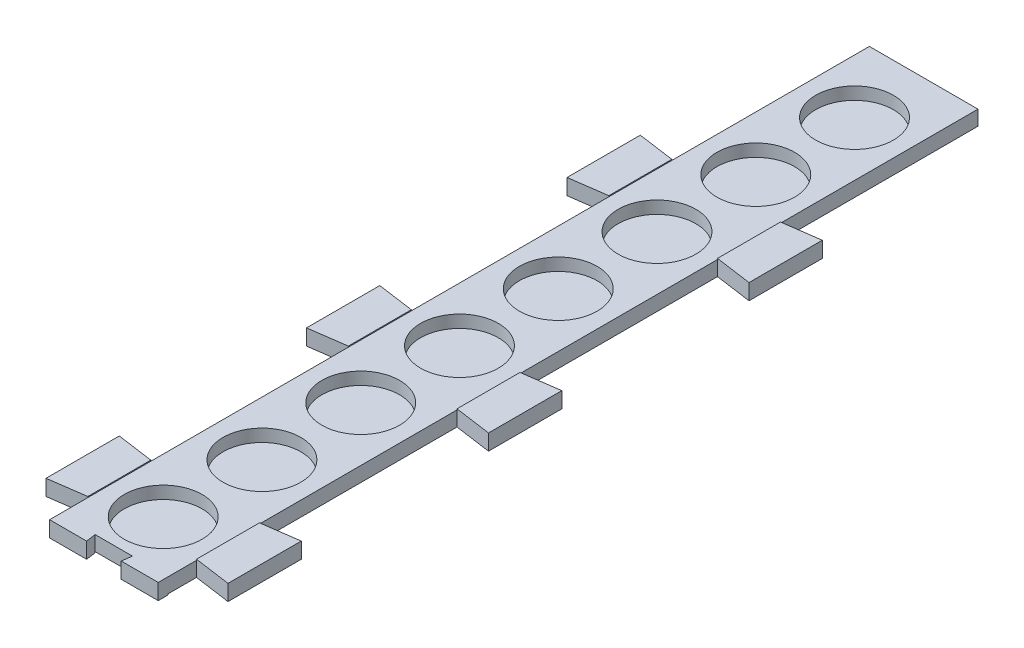
SolidWorks part; units mm, degrees
ref_plane "Front Plane" through (0, 0, 0) normal (0, 0, 1) x (1, 0, 0)
ref_plane "Top Plane" through (0, 0, 0) normal (0, 1, 0) x (1, 0, 0)
ref_plane "Right Plane" through (0, 0, 0) normal (1, 0, 0) x (0, 0, -1)
sketch "Sketch1" plane through (0, 0, 0) normal (0, 1, 0) x (1, 0, 0)
  line L1 (-13.97, -195.58) -> (13.97, -195.58)
  line L2 (-13.97, -195.58) -> (-13.97, 195.58)
  line L3 (-13.97, 195.58) -> (13.97, 195.58)
  line L4 (13.97, -195.58) -> (13.97, 195.58)
  line L5 (-13.97, -195.58) -> (13.97, 195.58) construction
  line L6 (-13.97, 195.58) -> (13.97, -195.58) construction
  point P0 (0, 0)
  dimension "D1" = 391.16
  dimension "D2" = 27.94
extrude "Boss-Extrude1" add sketch "Sketch1" along normal blind 3.81
sketch "Sketch2" plane through (0, 3.81, 0) normal (0, 1, 0) x (1, 0, 0)
  line L0 (-13.97, 195.58) -> (-13.97, -195.58) construction
  line L1 (13.97, 195.58) -> (-13.97, 195.58) construction
  line L3 (-13.97, -195.58) -> (13.97, -195.58) construction
  circle A0 centre (0, 177.8) radius 10
  circle A1 centre (0, 152.4) radius 10
  circle A2 centre (0, 127) radius 10
  circle A3 centre (0, 101.6) radius 10
  circle A4 centre (0, 76.2) radius 10
  circle A5 centre (0, 50.8) radius 10
  circle A6 centre (0, 25.4) radius 10
  circle A7 centre (0, 0) radius 10
  circle A8 centre (0, -25.4) radius 10
  circle A9 centre (0, -50.8) radius 10
  circle A10 centre (0, -76.2) radius 10
  circle A11 centre (0, -101.6) radius 10
  circle A12 centre (0, -127) radius 10
  circle A13 centre (0, -152.4) radius 10
  circle A14 centre (0, -177.8) radius 10
  dimension "D1" = 20
  dimension "D2" = 13.97
  dimension "D4" = 17.78
  dimension "D5" = 17.78
  dimension "D3" = 15
extrude "Cut-Extrude1" cut sketch "Sketch2" against normal blind 3.21
sketch "Sketch4" plane through (0, 0, 0) normal (0, 1, 0) x (1, 0, 0)
  line L0 (13.97, -56.2067) -> (23.4023, -54.881)
  line L2 (13.97, -195.58) -> (13.97, 195.58) construction
  line L5 (13.97, 144.78) -> (13.97, 128.5844)
  line L6 (0, 195.58) -> (0, -195.58) construction
  line L7 (13.97, 195.58) -> (-13.97, 195.58) construction
  line L8 (-13.97, -195.58) -> (13.97, -195.58) construction
  line L9 (13.97, -56.2067) -> (13.97, -72.4022)
  line L30 (-13.97, 144.78) -> (-13.97, 128.5844)
  line L31 (13.97, 144.78) -> (23.4023, 146.1056)
  line L32 (-13.97, 128.5844) -> (-23.4023, 127.2588)
  line L33 (13.97, 128.5844) -> (23.4023, 127.2588)
  line L34 (23.4023, 146.1056) -> (23.4023, 127.2588)
  line L35 (13.97, 144.78) -> (13.97, 128.5844)
  line L36 (13.97, 144.78) -> (13.97, 128.5844)
  line L37 (23.4023, 127.2588) -> (23.4023, 146.1056)
  line L38 (13.97, 144.78) -> (23.4023, 146.1056)
  line L39 (-13.97, 144.78) -> (-23.4023, 146.1056)
  line L40 (-23.4023, 127.2588) -> (-23.4023, 146.1056)
  line L41 (-23.4023, 146.1056) -> (-23.4023, 127.2588)
  line L42 (13.97, 77.7844) -> (23.4023, 79.1101)
  line L43 (13.97, 77.7844) -> (13.97, 61.5889)
  line L44 (13.97, 61.5889) -> (23.4023, 60.2633)
  line L45 (23.4023, 79.1101) -> (23.4023, 60.2633)
  line L46 (13.97, 10.7889) -> (23.4023, 12.1145)
  line L47 (13.97, 10.7889) -> (13.97, -5.4067)
  line L48 (13.97, -5.4067) -> (23.4023, -6.7323)
  line L49 (23.4023, 12.1145) -> (23.4023, -6.7323)
  line L50 (-13.97, 10.7889) -> (-13.97, -5.4067)
  line L51 (-13.97, -5.4067) -> (-23.4023, -6.7323)
  line L52 (-23.4023, 12.1145) -> (-23.4023, -6.7323)
  line L53 (-13.97, 10.7889) -> (-23.4023, 12.1145)
  line L54 (-13.97, 77.7844) -> (-13.97, 61.5889)
  line L55 (-13.97, 61.5889) -> (-23.4023, 60.2633)
  line L56 (-23.4023, 79.1101) -> (-23.4023, 60.2633)
  line L57 (-13.97, 77.7844) -> (-23.4023, 79.1101)
  line L58 (13.97, -72.4022) -> (23.4023, -73.7278)
  line L59 (23.4023, -54.881) -> (23.4023, -73.7278)
  line L60 (13.97, -123.2022) -> (23.4023, -121.8766)
  line L61 (13.97, -123.2022) -> (13.97, -139.3978)
  line L62 (13.97, -139.3978) -> (23.4023, -140.7234)
  line L63 (23.4023, -121.8766) -> (23.4023, -140.7234)
  line L72 (-13.97, -123.2022) -> (-13.97, -139.3978)
  line L73 (-13.97, -139.3978) -> (-23.4023, -140.7234)
  line L74 (-23.4023, -121.8766) -> (-23.4023, -140.7234)
  line L75 (-13.97, -123.2022) -> (-23.4023, -121.8766)
  line L76 (-13.97, -56.2067) -> (-13.97, -72.4022)
  line L77 (-13.97, -72.4022) -> (-23.4023, -73.7278)
  line L78 (-23.4023, -54.881) -> (-23.4023, -73.7278)
  line L79 (-13.97, -56.2067) -> (-23.4023, -54.881)
  line L80 (13.97, 144.78) -> (23.4023, 144.78) construction
  line L81 (13.97, 128.5844) -> (23.4023, 128.5844) construction
  dimension "D1" = 8
  dimension "D2" = 8
  dimension "D3" = 9.525
  dimension "D4" = 18.8468
  dimension "D5" = 50.8
  dimension "D6" = 5
  dimension "D7" = 50.8
extrude "Boss-Extrude2" add sketch "Sketch4" along normal blind 4.064 contours L54 L57 L56 L55 | L50 L53 L52 L51 | L49 L46 L47 L48 | L40 L32 L30 L39 | L34 L31 L5 L33 | L45 L44 L43 L42 | L76 L77 L78 L79 | L0 L59 L58 L9 | L60 L63 L62 L61 | L72 L73 L74 L75 region at (18.8051, 0, -136.6822) region at (-18.8051, 0, -136.6822) region at (18.8051, 0, -2.6911) region at (-18.8051, 0, -2.6911) region at (-18.8051, 0, -69.6867)
sketch "Sketch5" plane through (0, 0, 195.58) normal (0, 0, 1) x (1, 0, 0)
  line L1 (-23.4023, 0) -> (23.4023, 0)
  line L2 (-23.4023, 0) -> (-23.4023, 4.064)
  line L3 (-23.4023, 4.064) -> (23.4023, 4.064)
  line L4 (23.4023, 0) -> (23.4023, 4.064)
extrude "Cut-Extrude2" cut sketch "Sketch5" against normal blind 182.88
sketch "Sketch6" plane through (0, 3.81, 0) normal (0, 1, 0) x (1, 0, 0)
  line L0 (-4.802, -12.7) -> (-4.445, -15.24)
  line L1 (13.97, -12.7) -> (-13.97, -12.7) construction
  line L2 (-4.445, -15.24) -> (-13.97, -15.24)
  line L3 (-13.97, -15.24) -> (-13.97, -12.7)
  line L4 (-4.802, -12.7) -> (-4.802, -15.24) construction
  line L5 (13.97, -12.7) -> (13.97, -15.24)
  line L6 (13.97, -15.24) -> (4.445, -15.24)
  line L7 (4.445, -15.24) -> (4.802, -12.7)
  line L8 (4.802, -12.7) -> (4.802, -15.24) construction
  line L9 (-13.97, -12.7) -> (-4.802, -12.7)
  line L10 (4.802, -12.7) -> (13.97, -12.7)
  dimension "D1" = 8
  dimension "D2" = 9.525
  dimension "D3" = 2.54
  dimension "D4" = 8
  dimension "D5" = 2.54
  dimension "D6" = 9.525
extrude "Boss-Extrude3" add sketch "Sketch6" against normal blind 4.064
sketch "Sketch7" plane through (0, 0, 15.24) normal (0, 0, 1) x (1, 0, 0)
  line L0 (-23.4023, 4.064) -> (-23.4023, 0) construction
  line L1 (23.4023, 4.064) -> (23.4023, 0) construction
  line L2 (-13.97, -0.254) -> (-4.445, -0.254) construction
  line L3 (4.445, -0.254) -> (13.97, -0.254) construction
  circle A0 centre (-7.5273, 1.778) radius 1.27
  circle A1 centre (7.5273, 1.778) radius 1.27
  dimension "D3" = 2.54
  dimension "D4" = 2.54
  dimension "D1" = 15.875
  dimension "D2" = 15.875
  dimension "D5" = 2.032
  dimension "D6" = 2.032
